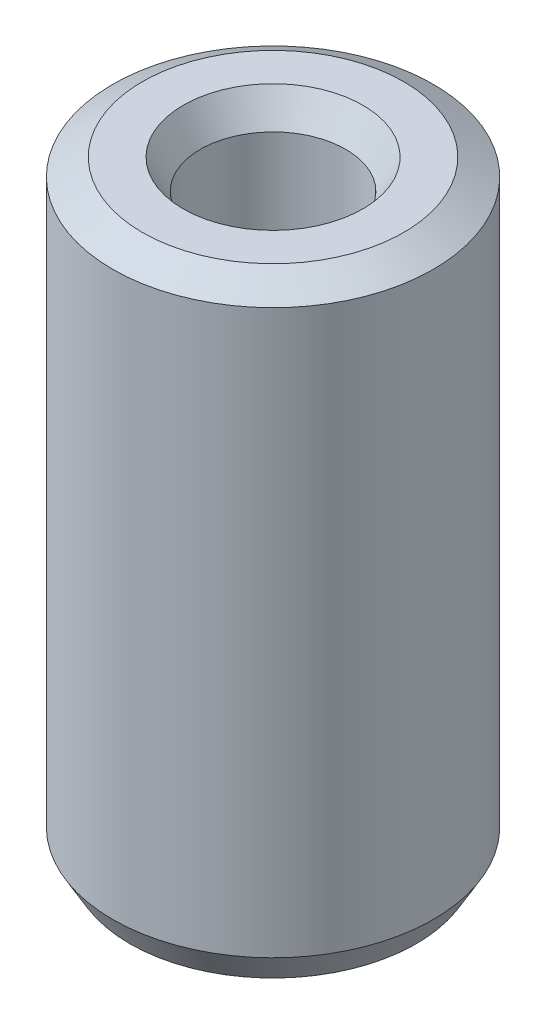
SolidWorks part; units mm, degrees
ref_plane "Front Plane" through (0, 0, 0) normal (0, 0, 1) x (1, 0, 0)
ref_plane "Top Plane" through (0, 0, 0) normal (0, 1, 0) x (1, 0, 0)
ref_plane "Right Plane" through (0, 0, 0) normal (1, 0, 0) x (0, 0, -1)
sketch "Sketch1" plane through (0, 0, 0) normal (0, 1, 0) x (1, 0, 0)
  circle A0 centre (0, 0) radius 15
  dimension "SLEEVE_OD" = 30
extrude "Boss-Extrude1" add sketch "Sketch1" along normal blind 57.059
sketch "Sketch2" plane through (0, 0, 0) normal (0, 1, 0) x (1, 0, 0)
  circle A0 centre (0, 0) radius 6.8054
  dimension "BORE_D" = 13.6108
extrude "Cut-Extrude1" cut sketch "Sketch2" along normal through all
chamfer "Chamfer1" distance 1.6014 angle 60 4 edges at (0, 57.059, 6.8054) (0, 0, 6.8054) (0, 0, 15) (0, 57.059, 15) first distance on face at (0, 57.059, 6.8054) first distance on face at (0, 0, 6.8054) first distance on face at (0, 57.059, 15)
